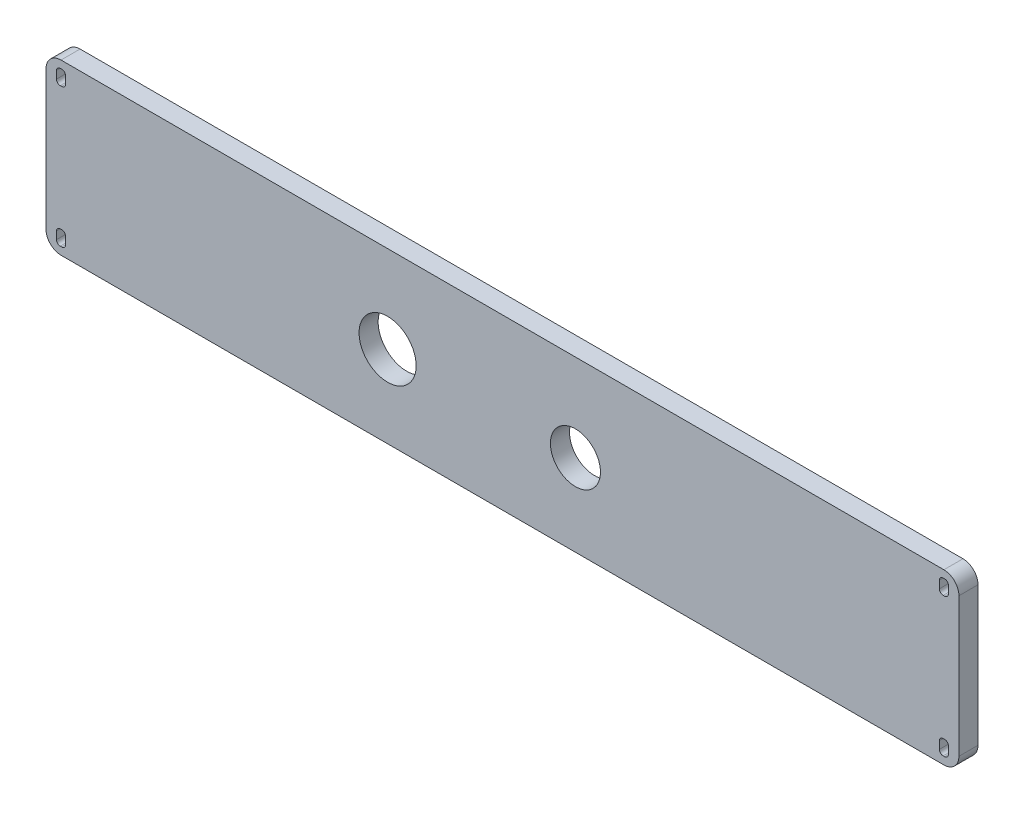
SolidWorks part; units mm, degrees
ref_plane "Front Plane" through (0, 0, 0) normal (0, 0, 1) x (1, 0, 0)
ref_plane "Top Plane" through (0, 0, 0) normal (0, 1, 0) x (1, 0, 0)
ref_plane "Right Plane" through (0, 0, 0) normal (1, 0, 0) x (0, 0, -1)
sketch "Sketch1" plane through (0, 0, 0) normal (0, 0, 1) x (1, 0, 0)
  line L0 (334.3524, 24.5402) -> (333.3524, 24.5402)
  line L1 (-263.7156, 132.0622) -> (343.8524, 132.0622)
  line L2 (-263.7156, 132.0622) -> (-263.7156, 19.5402)
  line L3 (-263.7156, 19.5402) -> (343.8524, 19.5402)
  line L4 (343.8524, 132.0622) -> (343.8524, 19.5402)
  line L5 (336.8524, 27.0402) -> (336.8524, 32.0402)
  line L6 (334.3524, 34.5402) -> (333.3524, 34.5402)
  line L7 (330.8524, 27.0402) -> (330.8524, 32.0402)
  line L8 (333.8524, 34.5402) -> (333.8524, 24.5402) construction
  line L9 (330.8524, 29.5402) -> (336.8524, 29.5402) construction
  line L10 (-253.2176, 24.5402) -> (-254.2176, 24.5402)
  line L11 (-256.7176, 27.0402) -> (-256.7176, 32.0402)
  line L12 (-253.2176, 34.5402) -> (-254.2176, 34.5402)
  line L13 (-250.7176, 27.0402) -> (-250.7176, 32.0402)
  line L14 (-253.2176, 117.0602) -> (-254.2176, 117.0602)
  line L15 (-256.7176, 119.5602) -> (-256.7176, 124.5602)
  line L16 (-253.2176, 127.0602) -> (-254.2176, 127.0602)
  line L17 (-250.7176, 119.5602) -> (-250.7176, 124.5602)
  line L18 (334.3524, 117.0602) -> (333.3524, 117.0602)
  line L19 (330.8524, 119.5602) -> (330.8524, 124.5602)
  line L20 (334.3524, 127.0602) -> (333.3524, 127.0602)
  line L21 (336.8524, 119.5602) -> (336.8524, 124.5602)
  arc A0 (334.3524, 24.5402) -> (336.8524, 27.0402) centre (334.3524, 27.0402) ccw
  arc A1 (336.8524, 32.0402) -> (334.3524, 34.5402) centre (334.3524, 32.0402) ccw
  arc A2 (333.3524, 24.5402) -> (330.8524, 27.0402) centre (333.3524, 27.0402) cw
  arc A3 (333.3524, 34.5402) -> (330.8524, 32.0402) centre (333.3524, 32.0402) ccw
  arc A4 (-254.2176, 24.5402) -> (-256.7176, 27.0402) centre (-254.2176, 27.0402) cw
  arc A5 (-254.2176, 34.5402) -> (-256.7176, 32.0402) centre (-254.2176, 32.0402) ccw
  arc A6 (-250.7176, 32.0402) -> (-253.2176, 34.5402) centre (-253.2176, 32.0402) ccw
  arc A7 (-253.2176, 24.5402) -> (-250.7176, 27.0402) centre (-253.2176, 27.0402) ccw
  arc A8 (-254.2176, 117.0602) -> (-256.7176, 119.5602) centre (-254.2176, 119.5602) cw
  arc A9 (-254.2176, 127.0602) -> (-256.7176, 124.5602) centre (-254.2176, 124.5602) ccw
  arc A10 (-250.7176, 124.5602) -> (-253.2176, 127.0602) centre (-253.2176, 124.5602) ccw
  arc A11 (-253.2176, 117.0602) -> (-250.7176, 119.5602) centre (-253.2176, 119.5602) ccw
  arc A12 (333.3524, 117.0602) -> (330.8524, 119.5602) centre (333.3524, 119.5602) cw
  arc A13 (333.3524, 127.0602) -> (330.8524, 124.5602) centre (333.3524, 124.5602) ccw
  arc A14 (336.8524, 124.5602) -> (334.3524, 127.0602) centre (334.3524, 124.5602) ccw
  arc A15 (334.3524, 117.0602) -> (336.8524, 119.5602) centre (334.3524, 119.5602) ccw
  circle A16 centre (88.6326, 74.0187) radius 16.65
  circle A17 centre (-36.3674, 74.0187) radius 19
  dimension "D5" = 2.5
  dimension "D18" = 33.3
  dimension "D19" = 58.0435
  dimension "D13" = 58.0435
  dimension "D14" = 38
  dimension "D15" = 227.3482
  dimension "D16" = 125
  dimension "D1" = 132.0622
  dimension "23.92in" = 607.568
  dimension "4.4" = 112.522
  dimension "D2" = 343.8524
  dimension "D3" = 6
  dimension "D4" = 10
  dimension "D6" = 10
  dimension "D7" = 10
  dimension "D10" = 7
  dimension "D11" = 5.002
  dimension "D12" = 6.998
  dimension "D8" = 2
  dimension "D9" = 2
extrude "Boss-Extrude1" add sketch "Sketch1" along normal blind 12.7 contours L7 A3 L6 A1 L5 A0 L0 A2 | L2 L3 L4 L1 | L11 A5 L12 A6 L13 A7 L10 A4 | L15 A9 L16 A10 L17 A11 L14 A8 | L19 A13 L20 A14 L21 A15 L18 A12 | A16 | A17
fillet "Fillet1" radius 10 4 edges at (343.8524, 19.5402, 6.35) (343.8524, 132.0622, 6.35) (-263.7156, 19.5402, 6.35) (-263.7156, 132.0622, 6.35)
